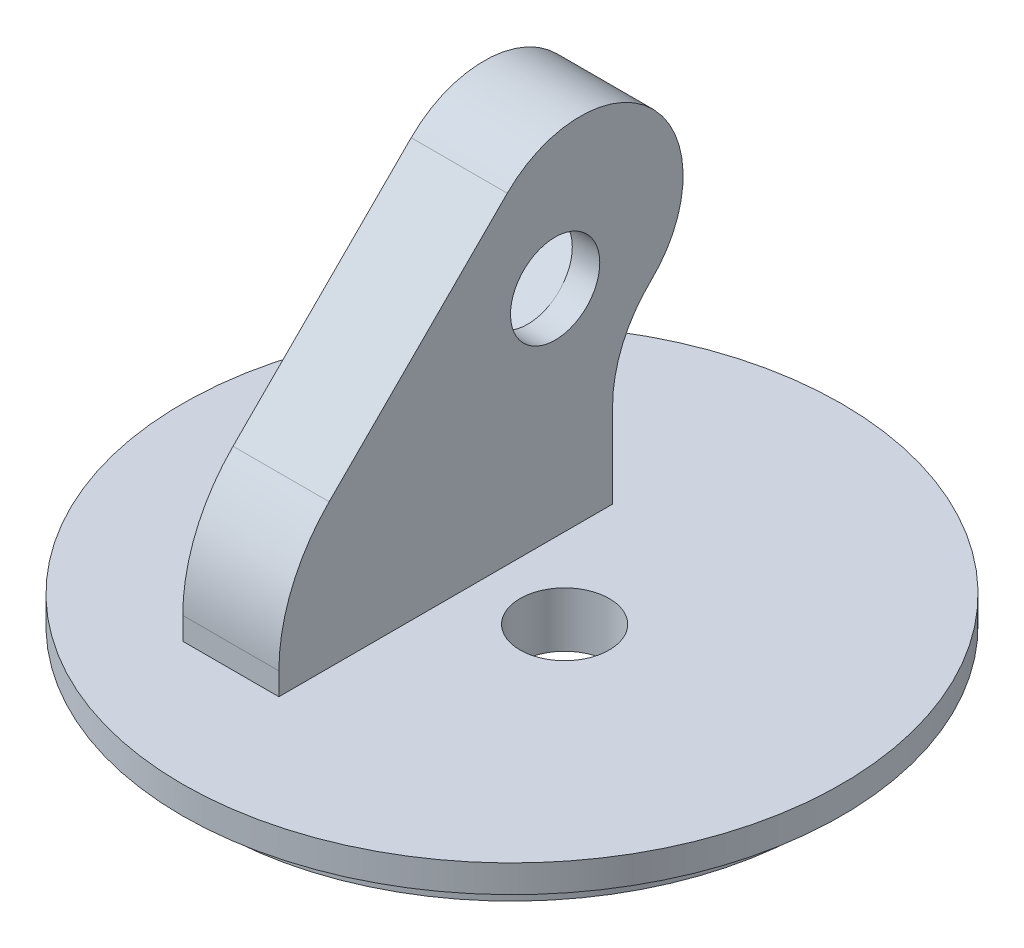
SolidWorks part; units mm, degrees
ref_plane "Front Plane" through (0, 0, 0) normal (0, 0, 1) x (1, 0, 0)
ref_plane "Top Plane" through (0, 0, 0) normal (0, 1, 0) x (1, 0, 0)
ref_plane "Right Plane" through (0, 0, 0) normal (1, 0, 0) x (0, 0, -1)
sketch "Sketch2" plane through (0, 0, 0) normal (0, 1, 0) x (1, 0, 0)
  circle A0 centre (0, 0) radius 48
  dimension "D1" = 96
extrude "Boss-Extrude1" add sketch "Sketch2" along normal blind 4
ref_plane "Plane1" through (-4, 0, 0) normal (1, 0, 0) x (0, 0, -1)
sketch "Sketch7" plane through (-4, 0, 0) normal (1, 0, 0) x (0, 0, -1)
  line L0 (18.6521, 16.3561) -> (18.6521, 4)
  line L5 (48, 4) -> (-48, 4) construction
  line L6 (-22.6311, 24.9401) -> (3.3119, 50.8831)
  line L7 (-43.5609, 4) -> (18.6521, 4)
  line L11 (-29.9535, 4) -> (-29.9535, 7.2624)
  arc A4 (24.252, 29.4036) -> (3.3119, 50.8831) centre (13.9185, 40.2765) ccw
  arc A5 (24.252, 29.4036) -> (18.6521, 16.3561) centre (36.6521, 16.3561) ccw
  arc A6 (-22.6311, 24.9401) -> (-29.9535, 7.2624) centre (-4.9535, 7.2624) ccw
  dimension "D1" = 25
  dimension "D4" = 30
  dimension "D3" = 18
  dimension "D5" = 45
extrude "Boss-Extrude2" add sketch "Sketch7" against normal blind 14 contours A5 A4 L6 L7 L0 | A4 | A4 | A4 | L6 A6 L7 region at (-4, 26.0967, -1.8639)
ref_plane "Plane2" through (-6, 0, 0) normal (1, 0, 0) x (0, 0, -1)
sketch "Sketch31" plane through (-18, 10.4618, -5.3595) normal (-1, 0, 0) x (0, 0, 1)
  line L0 (-5.4155, 34.0546) -> (11.7496, 18.7458)
  line L1 (11.7496, 18.7458) -> (3.0968, 9.0438)
  line L2 (3.0968, 9.0438) -> (-14.0683, 24.3526)
  line L3 (-14.0683, 24.3526) -> (-5.4155, 34.0546)
  circle A0 centre (-4.9225, 24.9054) radius 6.5
  dimension "D1" = 6.5
extrude "Cut-Extrude18" cut sketch "Sketch31" against normal through all contours A0
extrude "Cut-Extrude19" cut sketch "Sketch31<3>" against normal blind 10 contours L0 L1 L2 L3
sketch "Sketch31<3>" plane through (-18, 10.4618, -5.3595) normal (-1, 0, 0) x (0, 0, 1) same geometry as "Sketch31"
sketch "Sketch32" plane through (-18, 0, 0) normal (-1, 0, 0) x (0, 0, 1)
  line L0 (6.3901, 29.2076) -> (-2.2627, 19.5056) construction
  circle A0 centre (-17.0806, 41.2645) radius 1
  circle A1 centre (3.9294, 22.6926) radius 1
  arc A3 (-14.6084, 40.2182) -> (-15.5944, 39.1126) centre (-10.282, 35.3672) ccw construction
  dimension "D1" = 2.5
  dimension "D2" = 2.5
extrude "Cut-Extrude20" cut sketch "Sketch32" against normal blind 4.5
sketch "Sketch33" plane through (0, 0, 0) normal (0, -1, 0) x (1, 0, 0)
  circle A0 centre (0, 0) radius 43.5
extrude "Boss-Extrude3" add sketch "Sketch33" along normal blind 4
sketch "Sketch35" plane through (0, 4, 0) normal (0, 1, 0) x (1, 0, 0)
  circle A0 centre (7.6655, 0) radius 6.5
extrude "Cut-Extrude22" cut sketch "Sketch35" against normal through all
